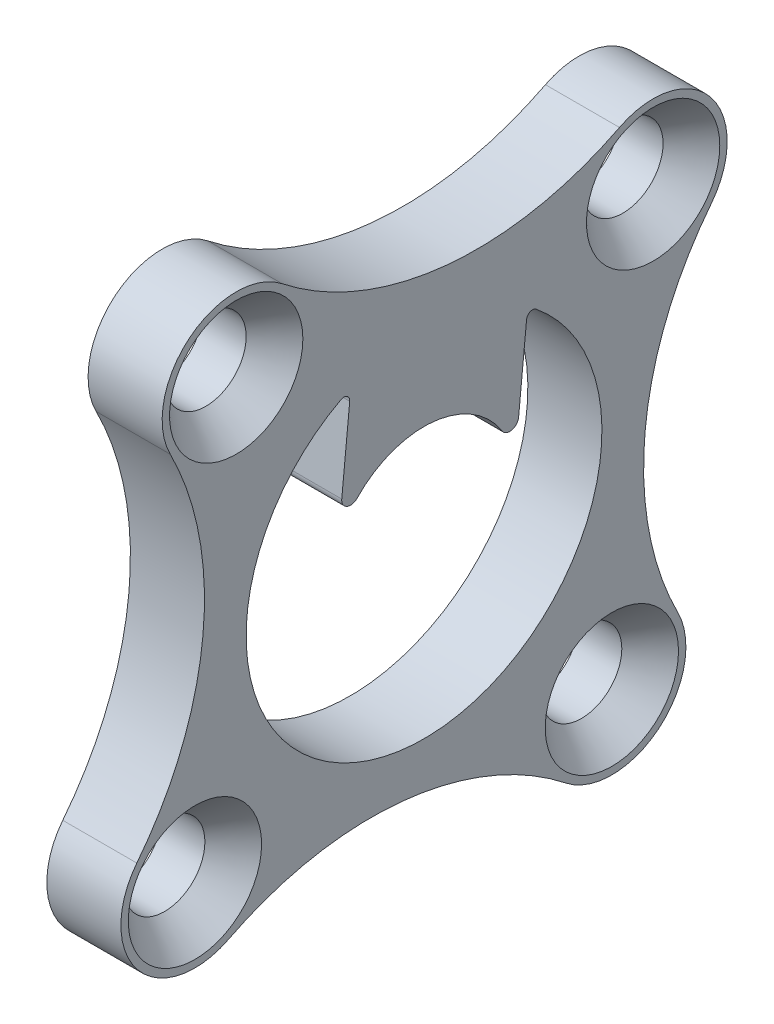
SolidWorks part; units mm, degrees
material "6061-T6 (SS)"
ref_plane "Front Plane" through (0, 0, 0) normal (0, 0, 1) x (1, 0, 0)
ref_plane "Top Plane" through (0, 0, 0) normal (0, 1, 0) x (1, 0, 0)
ref_plane "Right Plane" through (0, 0, 0) normal (1, 0, 0) x (0, 0, -1)
sketch "Sketch1" plane through (-42.315, 0, 0) normal (-1, 0, 0) x (0, 0, 1)
  line L0 (3.1855, 6.4972) -> (3.5279, 3.0385)
  line L1 (3.0189, 8.1803) -> (3.2006, 6.3452) construction
  line L2 (-4.0551, 2.2879) -> (-4.3974, 5.7466)
  line L3 (-4.564, 7.4297) -> (-4.0729, 2.4683) construction
  line L5 (3.2006, 6.3452) -> (3.682, 1.4811) construction
  line L6 (9.8212, -8.052) -> (-9.8212, 8.052) construction
  line L7 (-8.052, -9.8212) -> (8.052, 9.8212) construction
  arc A0 (3.5279, 3.0385) -> (2.8729, 2.7381) centre (3.1487, 3.001) cw
  arc A1 (2.8729, 2.7381) -> (-3.354, 2.1218) centre (0, 0) ccw
  arc A2 (-3.354, 2.1218) -> (-4.0551, 2.2879) centre (-3.6759, 2.3255) cw
  circle A3 centre (0, 0) radius 3.9687 construction
  circle A4 centre (0, 0) radius 3.9687 construction
  arc A5 (3.1855, 6.4972) -> (3.5567, 6.7469) centre (3.4383, 6.5222) cw
  arc A8 (3.5567, 6.7469) -> (-4.8104, 5.9187) centre (0, 0) cw
  arc A9 (-4.8104, 5.9187) -> (-4.3974, 5.7466) centre (-4.6502, 5.7216) cw
  circle A10 centre (0, 0) radius 15.875
  arc A11 (-4.7976, 5.7648) -> (3.5744, 6.5935) centre (0, 0) ccw construction
  circle A12 centre (8.052, 9.8212) radius 3.175 construction
  circle A13 centre (8.052, 9.8212) radius 2.6924 construction
  circle A14 centre (0, 0) radius 9.525 construction
  dimension "D1" = 0.381
  dimension "D2" = 0.254
  dimension "D3" = 25.4
  dimension "D4" = 0.127
  dimension "D6" = 5.3848
  dimension "D7" = 19.05
  dimension "D5" = 45
extrude "Boss-Extrude1" add sketch "Sketch1" against normal blind 3.175
sketch "Sketch2" plane through (-42.315, 0, 0) normal (-1, 0, 0) x (0, 0, 1)
  line L0 (-8.052, -9.8212) -> (8.052, 9.8212) construction
  line L1 (3.1855, 6.4972) -> (3.5279, 3.0385) construction
  line L2 (9.4787, 0.9382) -> (15.7978, 1.5637)
  arc A0 (10.065, 12.2765) -> (15.7978, 1.5637) centre (0, 0) cw
  circle A1 centre (0, 0) radius 15.875 construction
  circle A3 centre (0, 0) radius 9.525 construction
  arc A5 (10.881, 8.3799) -> (10.065, 12.2765) centre (8.052, 9.8212) ccw
  circle A6 centre (8.052, 9.8212) radius 3.175 construction
  arc A7 (10.881, 8.3799) -> (9.4787, 0.9382) centre (22.8836, 2.2651) ccw
extrude "Cut-Extrude1" cut sketch "Sketch2" against normal through all
mirror "Mirror1" about plane through (-39.14, 0.9382, 9.4787) normal (0, -0.9951, 0.0985) of "Cut-Extrude1"
pattern_circular "CirPattern2" count 4 over 360 about axis through (-42.315, 0, 0) along (-1, 0, 0) of "Cut-Extrude1", "Mirror1"
hole_wizard "CSK for #4 Flat Head Machine Screw1" positions "Sketch3" profile "Sketch4" countersink size "#4" standard "ANSI Inch" end condition up to next
sketch "Sketch3" plane through (-39.14, 0, 0) normal (1, 0, 0) x (0, 0, -1)
  point P0 (9.8212, 8.052)
  point P3 (9.8212, 8.052)
  point P6 (9.8212, 8.052)
  point P9 (9.8212, 8.052)
  point P13 (-8.052, 9.8212)
  point P16 (-9.8212, -8.052)
  point P19 (8.052, -9.8212)
sketch "Sketch4" plane through (-39.14, 8.052, -9.8212) normal (0, 1, 0) x (0, 0, -1)
  line L0 (0, 0) -> (0, 3.175)
  line L1 (0, 3.175) -> (1.7272, 3.175)
  line L2 (1.7272, 3.175) -> (1.7272, 1.3003)
  line L3 (1.7272, 1.3003) -> (2.8575, 0)
  line L5 (2.8575, 0) -> (0, 0)
  line L6 (-1.7272, 1.3003) -> (-2.8575, 0) construction
  line L11 (0, -6.35) -> (0, 107.95) construction
  dimension "Thru Hole Dia." = 3.4544
  dimension "Thru Hole Depth" = 3.175
  dimension "Near C'Sink Dia." = 5.715
  dimension "Near C'Sink Angle" = 82
